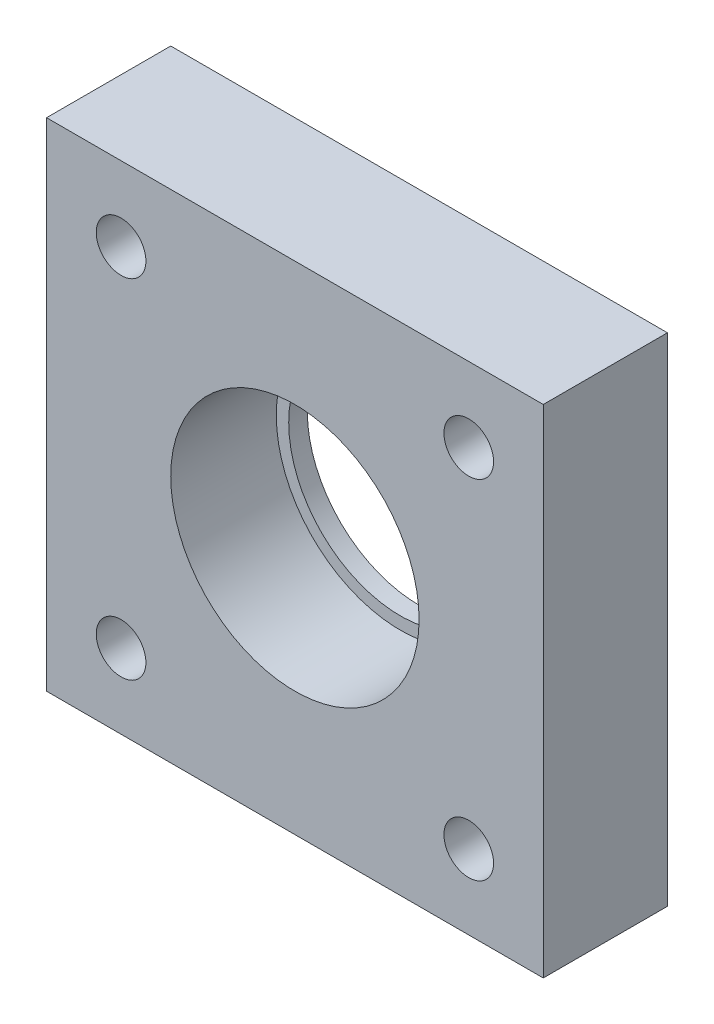
SolidWorks part; units mm, degrees
material "AISI 316 Annealed Stainless Steel Bar (SS)"
ref_plane "Front Plane" through (0, 0, 0) normal (0, 0, 1) x (1, 0, 0)
ref_plane "Top Plane" through (0, 0, 0) normal (0, 1, 0) x (1, 0, 0)
ref_plane "Right Plane" through (0, 0, 0) normal (1, 0, 0) x (0, 0, -1)
sketch "Sketch1" plane through (0, 0, 0) normal (0, 0, 1) x (1, 0, 0)
  line L1 (-20, -20) -> (20, -20)
  line L2 (-20, -20) -> (-20, 20)
  line L3 (-20, 20) -> (20, 20)
  line L4 (20, -20) -> (20, 20)
  line L5 (-20, -20) -> (20, 20) construction
  line L6 (-20, 20) -> (20, -20) construction
  circle A0 centre (0, 0) radius 10
  circle A1 centre (-14, 14) radius 2
  circle A2 centre (14, 14) radius 2
  circle A3 centre (14, -14) radius 2
  circle A4 centre (-14, -14) radius 2
  point P0 (0, 0)
  point P19 (0, 0)
  dimension "D1" = 20
  dimension "D2" = 4
  dimension "D5" = 6
  dimension "D6" = 4
  dimension "D3" = 40
  dimension "D4" = 40
extrude "Boss-Extrude1" add sketch "Sketch1" along normal blind 10 contours A4 L2 L1 L4 A2 L3 A3 A1 A0 region at (-19.4343, 0, 0)
sketch "Sketch2" plane through (0, 0, 0) normal (0, 0, -1) x (-1, 0, 0)
  circle A0 centre (0, 0) radius 10
  circle A1 centre (0, 0) radius 9
  dimension "D1" = 20
  dimension "D2" = 18
extrude "Boss-Extrude2" add sketch "Sketch2" against normal blind 1.5
